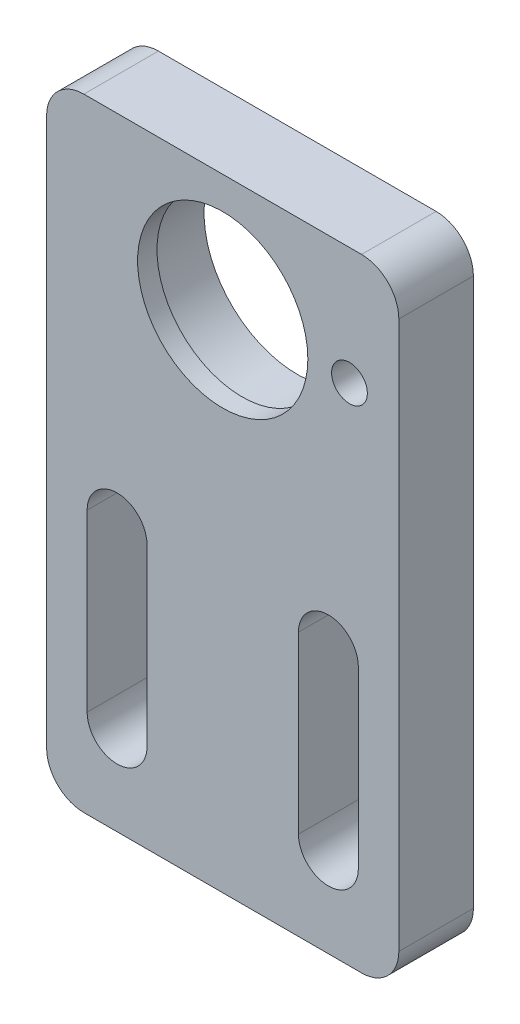
SolidWorks part; units mm, degrees
ref_plane "Front Plane" through (0, 0, 0) normal (0, 0, 1) x (1, 0, 0)
ref_plane "Top Plane" through (0, 0, 0) normal (0, 1, 0) x (1, 0, 0)
ref_plane "Right Plane" through (0, 0, 0) normal (1, 0, 0) x (0, 0, -1)
sketch "Sketch1" plane through (0, 0, 0) normal (0, 0, 1) x (1, 0, 0)
  line L58 (363.8587, 240.7839) -> (387.5087, 240.7839)
  line L75 (387.5087, 293.7839) -> (363.8587, 293.7839)
  line L81 (360.6837, 290.6089) -> (360.6837, 243.9589)
  line L83 (364.1337, 248.3339) -> (364.1337, 263.2339)
  line L84 (369.2337, 263.2339) -> (369.2337, 248.3339)
  line L85 (382.1337, 263.2339) -> (382.1337, 248.3339)
  line L86 (387.2337, 248.3339) -> (387.2337, 263.2339)
  line L87 (390.6837, 243.9589) -> (390.6837, 290.6089)
  circle A123 centre (375.6837, 283.7839) radius 7.9375
  circle A124 centre (375.6837, 283.7839) radius 7.25
  arc A126 (360.6837, 243.9589) -> (363.8587, 240.7839) centre (363.8587, 243.9589) ccw
  arc A127 (387.5087, 240.7839) -> (390.6837, 243.9589) centre (387.5087, 243.9589) ccw
  arc A128 (390.6837, 290.6089) -> (387.5087, 293.7839) centre (387.5087, 290.6089) ccw
  arc A129 (363.8587, 293.7839) -> (360.6837, 290.6089) centre (363.8587, 290.6089) ccw
  arc A134 (364.1337, 248.3339) -> (369.2337, 248.3339) centre (366.6837, 248.3339) ccw
  arc A135 (369.2337, 263.2339) -> (364.1337, 263.2339) centre (366.6837, 263.2339) ccw
  arc A136 (387.2337, 263.2339) -> (382.1337, 263.2339) centre (384.6837, 263.2339) ccw
  arc A137 (382.1337, 248.3339) -> (387.2337, 248.3339) centre (384.6837, 248.3339) ccw
  circle A147 centre (386.4787, 283.7839) radius 1.524
extrude "Boss-Extrude1" add sketch "Sketch1" along normal blind 6.35 contours L75 A129 L81 A126 L58 A127 L87 A128 A147 A137 L85 A136 L86 A135 L84 A134 L83 A123 | A123 A124 region at (375.6171, 266.2962, 0) region at (367.9707, 283.7839, 0)
extrude "Cut-Extrude1" cut sketch "Sketch1<3>" along normal blind 4.699 contours A123 A124 region at (367.9707, 283.7839, 0)
sketch "Sketch1<3>" plane through (0, 0, 0) normal (0, 0, 1) x (1, 0, 0) same geometry as "Sketch1"
